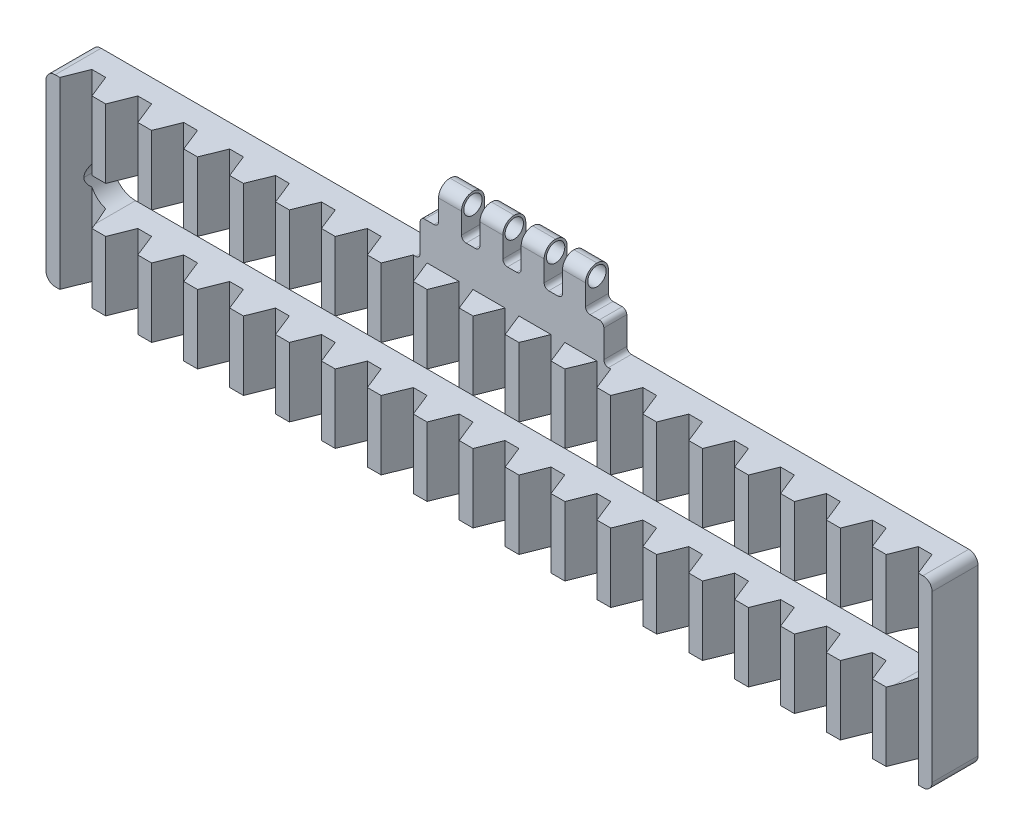
SolidWorks part; units mm, degrees
ref_plane "Front" through (0, 0, 0) normal (0, 0, 1) x (1, 0, 0)
ref_plane "Top" through (0, 0, 0) normal (0, 1, 0) x (1, 0, 0)
ref_plane "Right" through (0, 0, 0) normal (1, 0, 0) x (0, 0, -1)
sketch "Sketch1" plane through (0, 0, 0) normal (0, 1, 0) x (1, 0, 0)
  line L1 (96.5, -5) -> (-96.5, -5)
  line L2 (96.5, -5) -> (96.5, 5)
  line L3 (96.5, 5) -> (-96.5, 5)
  line L4 (-96.5, -5) -> (-96.5, 5)
  line L5 (96.5, -5) -> (-96.5, 5) construction
  line L6 (96.5, 5) -> (-96.5, -5) construction
  point P0 (0, 0)
  dimension "D1" = 10
  dimension "D2" = 193
extrude "Boss-Extrude1" add sketch "Sketch1" along normal blind 40
sketch "Sketch2" plane through (0, 0, 0) normal (0, 1, 0) x (1, 0, 0)
  line L0 (-96.5, -5) -> (-93.5, -5)
  line L1 (-96.5, -5) -> (96.5, -5) construction
  line L2 (-93.5, -5) -> (-91.5, 0)
  line L3 (-91.5, 0) -> (-88.5, 0)
  line L4 (-88.5, 0) -> (-86.5, -5)
  line L5 (-86.5, -5) -> (-83.5, -5)
  line L6 (-83.5, -5) -> (-81.5, 0)
  line L7 (-81.5, 0) -> (-78.5, 0)
  line L8 (-78.5, 0) -> (-76.5, -5)
  line L9 (-76.5, -5) -> (-73.5, -5)
  line L10 (-73.5, -5) -> (-71.5, 0)
  line L11 (-71.5, 0) -> (-68.5, 0)
  line L12 (-68.5, 0) -> (-66.5, -5)
  line L13 (-66.5, -5) -> (-63.5, -5)
  line L14 (-63.5, -5) -> (-61.5, 0)
  line L15 (-61.5, 0) -> (-58.5, 0)
  line L16 (-58.5, 0) -> (-56.5, -5)
  line L17 (-56.5, -5) -> (-53.5, -5)
  line L18 (-53.5, -5) -> (-51.5, 0)
  line L19 (-51.5, 0) -> (-48.5, 0)
  line L20 (-48.5, 0) -> (-46.5, -5)
  line L21 (-46.5, -5) -> (-43.5, -5)
  line L22 (-43.5, -5) -> (-41.5, 0)
  line L23 (-41.5, 0) -> (-38.5, 0)
  line L24 (-38.5, 0) -> (-36.5, -5)
  line L25 (-36.5, -5) -> (-33.5, -5)
  line L26 (-33.5, -5) -> (-31.5, 0)
  line L27 (-31.5, 0) -> (-28.5, 0)
  line L28 (-28.5, 0) -> (-26.5, -5)
  line L29 (-26.5, -5) -> (-23.5, -5)
  line L30 (-23.5, -5) -> (-21.5, 0)
  line L31 (-21.5, 0) -> (-18.5, 0)
  line L32 (-18.5, 0) -> (-16.5, -5)
  line L33 (-16.5, -5) -> (-13.5, -5)
  line L34 (-13.5, -5) -> (-11.5, 0)
  line L35 (-11.5, 0) -> (-8.5, 0)
  line L36 (-8.5, 0) -> (-6.5, -5)
  line L37 (-6.5, -5) -> (-3.5, -5)
  line L38 (-3.5, -5) -> (-1.5, 0)
  line L39 (-1.5, 0) -> (1.5, 0)
  line L40 (1.5, 0) -> (3.5, -5)
  line L41 (3.5, -5) -> (6.5, -5)
  line L42 (6.5, -5) -> (8.5, 0)
  line L43 (8.5, 0) -> (11.5, 0)
  line L44 (11.5, 0) -> (13.5, -5)
  line L45 (13.5, -5) -> (16.5, -5)
  line L46 (16.5, -5) -> (18.5, 0)
  line L47 (18.5, 0) -> (21.5, 0)
  line L48 (21.5, 0) -> (23.5, -5)
  line L49 (23.5, -5) -> (26.5, -5)
  line L50 (26.5, -5) -> (28.5, 0)
  line L51 (28.5, 0) -> (31.5, 0)
  line L52 (31.5, 0) -> (33.5, -5)
  line L53 (33.5, -5) -> (36.5, -5)
  line L54 (36.5, -5) -> (38.5, 0)
  line L55 (38.5, 0) -> (41.5, 0)
  line L56 (41.5, 0) -> (43.5, -5)
  line L57 (43.5, -5) -> (46.5, -5)
  line L58 (46.5, -5) -> (48.5, 0)
  line L59 (48.5, 0) -> (51.5, 0)
  line L60 (51.5, 0) -> (53.5, -5)
  line L61 (53.5, -5) -> (56.5, -5)
  line L62 (56.5, -5) -> (58.5, 0)
  line L63 (58.5, 0) -> (61.5, 0)
  line L64 (61.5, 0) -> (63.5, -5)
  line L65 (63.5, -5) -> (66.5, -5)
  line L66 (66.5, -5) -> (68.5, 0)
  line L67 (68.5, 0) -> (71.5, 0)
  line L68 (71.5, 0) -> (73.5, -5)
  line L69 (73.5, -5) -> (76.5, -5)
  line L70 (76.5, -5) -> (78.5, 0)
  line L71 (78.5, 0) -> (81.5, 0)
  line L72 (81.5, 0) -> (83.5, -5)
  line L73 (83.5, -5) -> (86.5, -5)
  line L74 (86.5, -5) -> (88.5, 0)
  line L75 (88.5, 0) -> (91.5, 0)
  line L76 (91.5, 0) -> (93.5, -5)
  line L77 (93.5, -5) -> (96.5, -5)
  line L81 (-96.5, -5) -> (-96.5, -20.768)
  line L82 (-96.5, -20.768) -> (96.5, -20.768)
  line L83 (96.5, -20.768) -> (96.5, -5)
  line L84 (101.5, 0) -> (103.5, -5) [skipped]
  line L85 (98.5, 0) -> (101.5, 0) [skipped]
  line L86 (96.5, -5) -> (98.5, 0) [skipped]
  dimension "D1" = 5
  dimension "D2" = 2
  dimension "D3" = 3
  dimension "D4" = 2
  dimension "D5" = 3
  dimension "D6" = 20
  dimension "D7" = 3
  dimension "D8" = 193
extrude "Cut-Extrude1" cut sketch "Sketch2" along normal blind 44 contours L82 L83 L77 L76 L75 L74 L73 L72 L71 L70 L69 L68 L67 L66 L65 L64 L63 L62 L61 L60 L59 L58 L57 L56 L55 L54 L53 L52 L51 L50 L49 L48 L47 L46 L45 L44 L43 L42 L41 L40 L39 L38 L37 L36 L35 L34 L33 L32 region at (0, 0, 11.5271)
sketch "Sketch3" plane through (0, 0, 0) normal (0, 0, 1) x (1, 0, 0)
  line L1 (92, 15) -> (-92, 15)
  line L2 (92, 15) -> (92, 25)
  line L3 (92, 25) -> (-92, 25)
  line L4 (-92, 15) -> (-92, 25)
  line L5 (92, 15) -> (-92, 25) construction
  line L6 (92, 25) -> (-92, 15) construction
  line L7 (91.5, 40) -> (88.5, 40) construction
  point P7 (90, 40)
  dimension "D1" = 92
  dimension "D2" = 10
  dimension "D3" = 15
  dimension "D4" = 92
  dimension "D5" = 15
extrude "Cut-Extrude2" cut sketch "Sketch3" against normal mid plane 44
fillet "Fillet1" radius 5 4 edges at (92, 15, -1.875) (92, 25, -1.875) (-92, 15, -1.875) (-92, 25, -1.875)
ref_plane "Plane1" through (0, 0, -5) normal (0, 0, 1) x (1, 0, 0)
sketch "Sketch4" plane through (0, 0, -5) normal (0, 0, 1) x (1, 0, 0)
  line L1 (-92, 30) -> (92, 30)
  line L2 (-92, 30) -> (-92, 35)
  line L3 (-92, 35) -> (92, 35)
  line L4 (92, 30) -> (92, 35)
  line L5 (-92, 30) -> (92, 35) construction
  line L6 (-92, 35) -> (92, 30) construction
  line L7 (-92, 10) -> (92, 10)
  line L8 (-92, 10) -> (-92, 5)
  line L9 (-92, 5) -> (92, 5)
  line L10 (92, 10) -> (92, 5)
  line L11 (-92, 10) -> (92, 5) construction
  line L12 (-92, 5) -> (92, 10) construction
  line L13 (-92, 28.5) -> (92, 28.5)
  line L14 (-92, 28.5) -> (-92, 36.5)
  line L15 (-92, 36.5) -> (92, 36.5)
  line L16 (92, 28.5) -> (92, 36.5)
  line L17 (-92, 28.5) -> (92, 36.5) construction
  line L18 (-92, 36.5) -> (92, 28.5) construction
  line L19 (-92, 3.5) -> (92, 3.5)
  line L20 (-92, 3.5) -> (-92, 11.5)
  line L21 (-92, 11.5) -> (92, 11.5)
  line L22 (92, 3.5) -> (92, 11.5)
  line L23 (-92, 3.5) -> (92, 11.5) construction
  line L24 (-92, 11.5) -> (92, 3.5) construction
  point P0 (0, 32.5)
  point P5 (0, 7.5)
  point P10 (0, 32.5)
  point P16 (0, 7.5)
  dimension "D1" = 184
  dimension "D2" = 184
  dimension "D3" = 5
  dimension "D4" = 5
  dimension "D5" = 7.5
  dimension "D6" = 32.5
  dimension "D7" = 8
  dimension "D8" = 4
  dimension "D9" = 8
  dimension "D10" = 4
extrude "Cut-Extrude3" cut sketch "Sketch4" along normal blind 4 contours L1 L4 L3 L2 | L10 L7 L8 L9 region at (0, 32.5, -5) region at (0, 7.5, -5)
fillet "Fillet3" radius 2 4 edges at (96.5, 0, 0) (96.5, 40, 0) (-96.5, 40, 0) (-96.5, 0, 0)
extrude "Cut-Extrude4" cut sketch "Sketch4<4>" along normal blind 2 contours L3 L16 L15 L14 | L13 L16 L1 L14 | L7 L22 L21 L20 | L19 L22 L9 L20 region at (0, 29.25, -5) region at (0, 35.75, -5) region at (0, 10.75, -5) region at (0, 4.25, -5)
sketch "Sketch4<4>" plane through (0, 0, -5) normal (0, 0, 1) x (1, 0, 0) same geometry as "Sketch4"
fillet "Fillet4" radius 2.5 8 edges at (92, 35, -2) (92, 30, -2) (-92, 35, -2) (-92, 30, -2) (-92, 10, -2) (-92, 5, -2) (92, 10, -2) (92, 5, -2)
fillet "Fillet5" radius 4 8 edges at (-92, 3.5, -4) (-92, 11.5, -4) (-92, 28.5, -4) (-92, 36.5, -4) (92, 11.5, -4) (92, 3.5, -4) (92, 28.5, -4) (92, 36.5, -4)
sketch "Sketch5" plane through (0, 40, 0) normal (0, 1, 0) x (1, 0, 0)
  line L1 (20, 0) -> (-20, 0)
  line L2 (20, 0) -> (20, 5)
  line L3 (20, 5) -> (-20, 5)
  line L4 (-20, 0) -> (-20, 5)
  line L5 (20, 0) -> (-20, 5) construction
  line L6 (20, 5) -> (-20, 0) construction
  point P0 (0, 2.5)
  dimension "D1" = 5
  dimension "D2" = 40
extrude "Boss-Extrude2" add sketch "Sketch5" along normal blind 8
sketch "Sketch6" plane through (0, 48, 0) normal (0, 1, 0) x (1, 0, 0)
  line L0 (20, 5) -> (-20, 5) construction
  line L1 (-16, 5) -> (-11, 5)
  line L2 (-16, 5) -> (-16, 0)
  line L3 (-16, 0) -> (-11, 0)
  line L4 (-11, 5) -> (-11, 0)
  line L5 (-13.5, 0) -> (-13.5, 5) construction
  line L6 (-16, 2.5) -> (-11, 2.5) construction
  line L7 (-20, 0) -> (20, 0) construction
  line L8 (-20, 5) -> (-20, 0) construction
  point P240 (-13.5, 2.5)
  dimension "D1" = 4
  dimension "D2" = 5
extrude "Boss-Extrude3" add sketch "Sketch6" along normal blind 8
fillet "Fillet6" radius 2.5 2 edges at (-13.5, 56, -5) (-13.5, 56, 0)
pattern_linear "LPattern1" count 4 spacing 9 along (1, 0, 0) of "Boss-Extrude3", "Fillet6"
sketch "Sketch7" plane through (-16, 0, 0) normal (-1, 0, 0) x (0, 0, 1)
  circle A0 centre (-2.5, 53.5) radius 2
extrude "Cut-Extrude5" cut sketch "Sketch7" against normal through all both and the other way through all contours A0
fillet "Fillet7" radius 1 12 edges at (-11, 48, -2.5) (-2, 48, -2.5) (7, 48, -2.5) (-7, 48, -2.5) (2, 48, -2.5) (11, 48, -2.5) (-20, 48, -2.5) (-16, 48, -2.5) (16, 48, -2.5) (20, 48, -2.5) (-20, 40, -2.5) (20, 40, -2.5)
